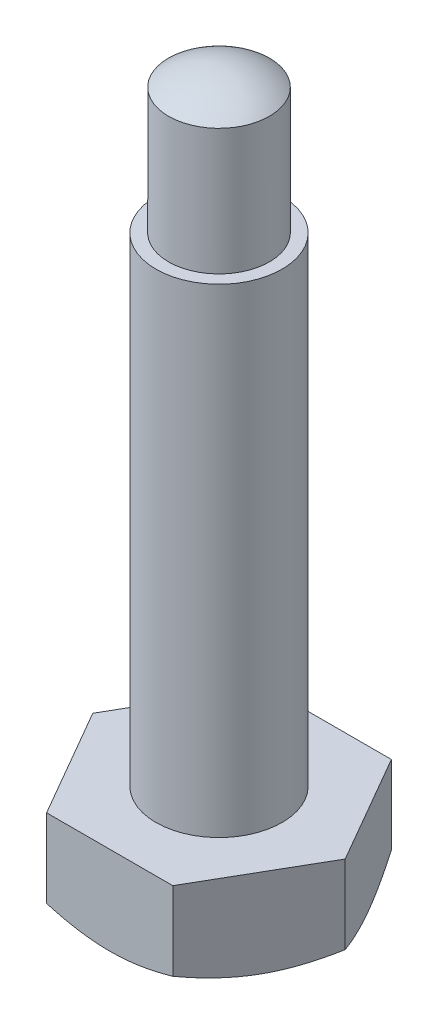
SolidWorks part; units mm, degrees
note: The reader was unsure of these and kept them because the rebuilt part matched: shared geometry of "Sketch1<3>", "Sketch1<4>".
ref_plane "Front Plane" through (0, 0, 0) normal (0, 0, 1) x (1, 0, 0)
ref_plane "Top Plane" through (0, 0, 0) normal (0, 1, 0) x (1, 0, 0)
ref_plane "Right Plane" through (0, 0, 0) normal (1, 0, 0) x (0, 0, -1)
sketch "Sketch1" plane through (0, 0, 0) normal (0, 1, 0) x (1, 0, 0)
  line L1 (15.0111, 0) -> (7.5056, 13)
  line L2 (7.5056, 13) -> (-7.5056, 13)
  line L3 (-7.5056, 13) -> (-15.0111, 0)
  line L4 (-15.0111, 0) -> (-7.5056, -13)
  line L5 (-7.5056, -13) -> (7.5056, -13)
  line L6 (7.5056, -13) -> (15.0111, 0)
  circle A0 centre (0, 0) radius 13 construction
  circle A1 centre (0, 0) radius 7.5
  circle A2 centre (0, 0) radius 6
extrude "Boss-Extrude1" add sketch "Sketch1" along normal blind 10.5 contours L5 L6 L1 L2 L3 L4 A1 | A2 | A1 A2
extrude "Boss-Extrude2" add sketch "Sketch1<3>" along normal blind 67.5 contours A1 A2
sketch "Sketch1<3>" plane through (0, 0, 0) normal (0, 1, 0) x (1, 0, 0) same geometry as "Sketch1"
extrude "Boss-Extrude3" add sketch "Sketch1<4>" along normal blind 82.5 contours A2
sketch "Sketch1<4>" plane through (0, 0, 0) normal (0, 1, 0) x (1, 0, 0) same geometry as "Sketch1"
cosmetic thread "Cosmetic Thread1" parameters "D2"=10.072
sketch "Sketch2" plane through (0, 0, 0) normal (0, 0, 1) x (1, 0, 0)
  line L0 (0, 82.5) -> (0, 84.5)
  line L1 (6, 82.5) -> (-6, 82.5) construction
  line L2 (-6, 82.5) -> (0, 82.5)
  arc A0 (0, 84.5) -> (-6, 82.5) centre (0, 74.5) ccw
revolve "Revolve1" add sketch "Sketch2" angle 360 about L0
sketch "Sketch4" plane through (0, 0, 0) normal (0, -1, 0) x (1, 0, 0)
  circle A0 centre (0, 0) radius 13
extrude "Cut-Extrude1" cut sketch "Sketch4" against normal blind 82.5 draft 60 flip side to cut
